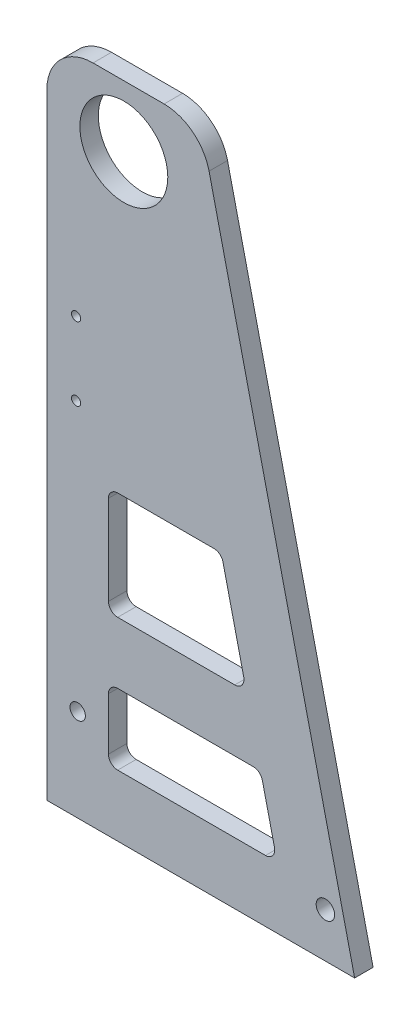
SolidWorks part; units mm, degrees
material "Policarbonato"
ref_plane "Plano frontal" through (0, 0, 0) normal (0, 0, 1) x (1, 0, 0)
ref_plane "Plano superior" through (0, 0, 0) normal (0, 1, 0) x (1, 0, 0)
ref_plane "Plano direito" through (0, 0, 0) normal (1, 0, 0) x (0, 0, -1)
sketch "Esboço1" plane through (0, 0, 0) normal (0, 0, 1) x (1, 0, 0)
  line L0 (0, 0) -> (0, 215)
  line L2 (100, 0) -> (0, 0)
  line L3 (0, 215) -> (50, 215)
  line L4 (50, 215) -> (100, 0)
  line L5 (10, 103) -> (10, 15) construction
  line L6 (25, 215) -> (25, 175) construction
  line L7 (10, 15) -> (75.7552, 15) construction
  line L8 (75.7552, 15) -> (55.2901, 103) construction
  line L9 (55.2901, 103) -> (10, 103) construction
  line L10 (20, 95) -> (20, 66)
  line L11 (23, 63) -> (61.0374, 63)
  line L12 (63.9594, 66.6795) -> (57.2152, 95.6795)
  line L13 (54.2932, 98) -> (23, 98)
  line L14 (20, 40) -> (20, 23)
  line L15 (23, 20) -> (71.0374, 20)
  line L16 (73.9594, 23.6795) -> (70.0059, 40.6795)
  line L17 (23, 43) -> (67.0839, 43)
  line L18 (0, 195) -> (50, 195) construction
  line L23 (17, 205) -> (33, 185) construction
  line L24 (17, 185) -> (33, 205) construction
  arc A8 (70.0059, 40.6795) -> (67.0839, 43) centre (67.0839, 40) ccw
  arc A9 (71.0374, 20) -> (73.9594, 23.6795) centre (71.0374, 23) ccw
  arc A10 (20, 23) -> (23, 20) centre (23, 23) ccw
  arc A11 (20, 40) -> (23, 43) centre (23, 40) cw
  arc A12 (57.2152, 95.6795) -> (54.2932, 98) centre (54.2932, 95) ccw
  arc A13 (61.0374, 63) -> (63.9594, 66.6795) centre (61.0374, 66) ccw
  arc A14 (20, 66) -> (23, 63) centre (23, 66) ccw
  arc A15 (20, 95) -> (23, 98) centre (23, 95) cw
  circle A20 centre (25, 195) radius 14.2875
  circle A21 centre (10, 30) radius 2.5
  point P8 (25, 195)
  point P16 (0, 200)
  point P17 (17, 210)
  point P18 (17, 210)
  point P49 (20, 63)
  dimension "D3" = 20
  dimension "D4" = 16
  dimension "D7" = 28.575
  dimension "D21" = 3
  dimension "D20" = 10
  dimension "D22" = 5
  dimension "D1" = 215
  dimension "D2" = 100
  dimension "D5" = 50
  dimension "D9" = 20
  dimension "D10" = 20
  dimension "D11" = 10
  dimension "D12" = 20
  dimension "D13" = 15
  dimension "D14" = 20
  dimension "D15" = 10
  dimension "D16" = 29
  dimension "D17" = 17
  dimension "D18" = 10
  dimension "D19" = 30
  dimension "D8" = 20
extrude "Ressalto-extrusão2" add sketch "Esboço1" along normal blind 6
fillet "Filete1" radius 15 2 edges at (0, 215, 3) (50, 215, 3)
sketch "Esboço3" plane through (0, 0, 0) normal (0, 0, -1) x (-1, 0, 0)
  circle A1 centre (-90.5, 14.5) radius 3
  ellipse E2 centre (-9.5, 117.2025) end of major axis (-8, 117.2025) minor radius 1.4266
  ellipse E3 centre (-9.5, 140.9789) end of major axis (-8, 140.9789) minor radius 1.4266
extrude "Corte-extrusão1" cut sketch "Esboço3" against normal through all
